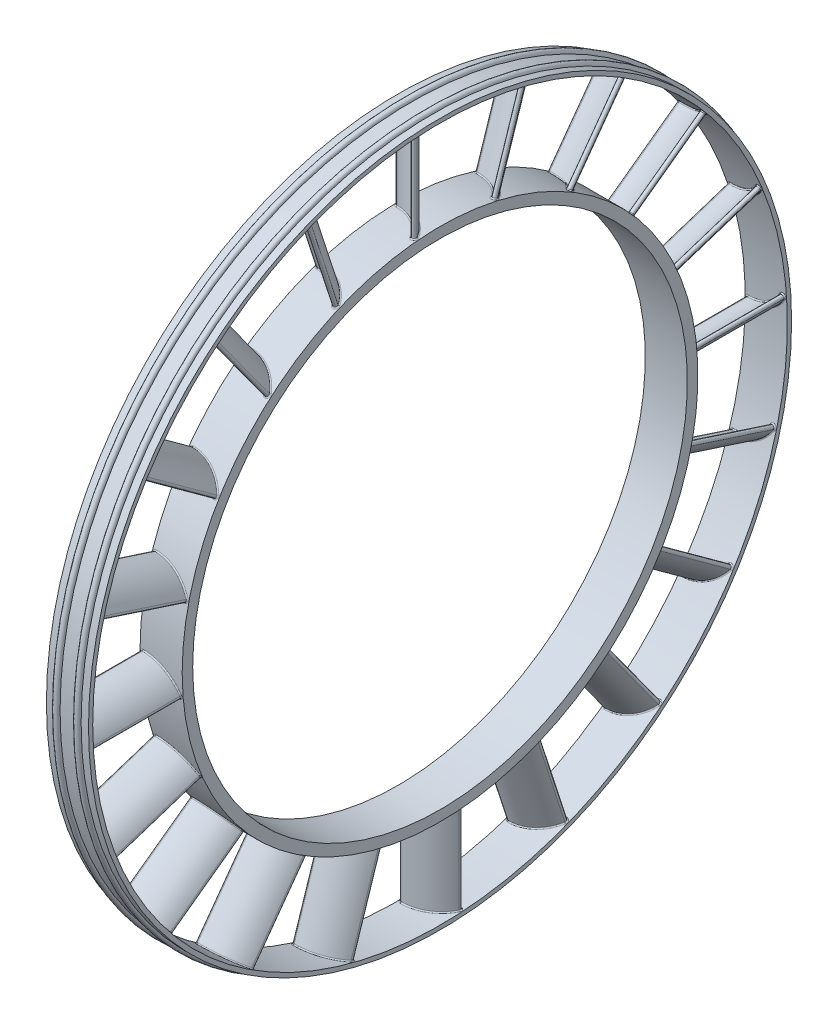
SolidWorks part; units mm, degrees
ref_plane "Front Plane" through (0, 0, 0) normal (0, 0, 1) x (1, 0, 0)
ref_plane "Top Plane" through (0, 0, 0) normal (0, 1, 0) x (1, 0, 0)
ref_plane "Right Plane" through (0, 0, 0) normal (1, 0, 0) x (0, 0, -1)
sketch "Sketch1" plane through (0, 0, 0) normal (0, 0, 1) x (1, 0, 0)
  line L0 (-118.8281, 0) -> (150.6493, 0) construction
  line L1 (-10, 117.5) -> (10, 117.5)
  line L2 (10, 117.5) -> (10, 122.5)
  line L3 (10, 122.5) -> (-10, 122.5)
  line L4 (-10, 122.5) -> (-10, 117.5)
  line L5 (-10, 165) -> (10, 165)
  line L6 (10, 165) -> (10, 167)
  line L7 (10, 167) -> (6.5, 167)
  line L8 (-10, 167) -> (-10, 165)
  line L9 (-6.5, 167) -> (-10, 167)
  line L10 (3.5, 167) -> (-3.5, 167)
  arc A0 (-3.5, 167) -> (-6.5, 167) centre (-5, 167) ccw
  arc A1 (6.5, 167) -> (3.5, 167) centre (5, 167) ccw
  point P5 (0, 117.5)
  point P10 (0, 165)
  dimension "D10" = 3
  dimension "D1" = 117.5
  dimension "D2" = 20
  dimension "D3" = 5
  dimension "D4" = 20
  dimension "D5" = 2
  dimension "D6" = 167
  dimension "D8" = 5
  dimension "D9" = 5
revolve "Revolve1" add sketch "Sketch1" angle 360 about L0
sketch "Sketch2" plane through (0, 0, 0) normal (0, 1, 0) x (1, 0, 0)
  line L0 (-10, 167) -> (-10, -167) construction
  line L1 (10, -167) -> (10, 167) construction
  arc A0 (-8.5, 0) -> (9, -10) centre (-8.321, -19.9992) cw
  arc A1 (-8.4821, -1.9999) -> (7.2679, -10.9999) centre (-8.321, -19.9992) cw
  arc A2 (-8.5, 0) -> (-8.4821, -1.9999) centre (-8.491, -1) ccw
  arc A3 (7.2679, -10.9999) -> (9, -10) centre (8.134, -10.5) ccw
  dimension "D3" = 20
  dimension "D1" = 1.5
  dimension "D2" = 1
  dimension "D4" = 10
  dimension "D5" = 2
extrude "Boss-Extrude1" add sketch "Sketch2" along normal up to surface (46.1967 mm away) from offset 118.5
fillet "Fillet1" radius 0.5 8 edges at (8.6715, 121.9737, 11.3432) (-3.9752, 122.4738, 2.5317) (-9.4667, 122.4975, 0.7804) (1.0625, 122.4777, 2.3371) (8.7296, 164.6124, 11.3032) (2.7942, 164.8966, 5.841) (-9.4832, 164.9962, 1.1246) (-1.0028, 164.9942, 1.3862)
pattern_circular "CirPattern1" count 20 over 360 about axis through (-118.8281, 0, 0) along (-1, 0, 0) of "Fillet1", "Boss-Extrude1"
